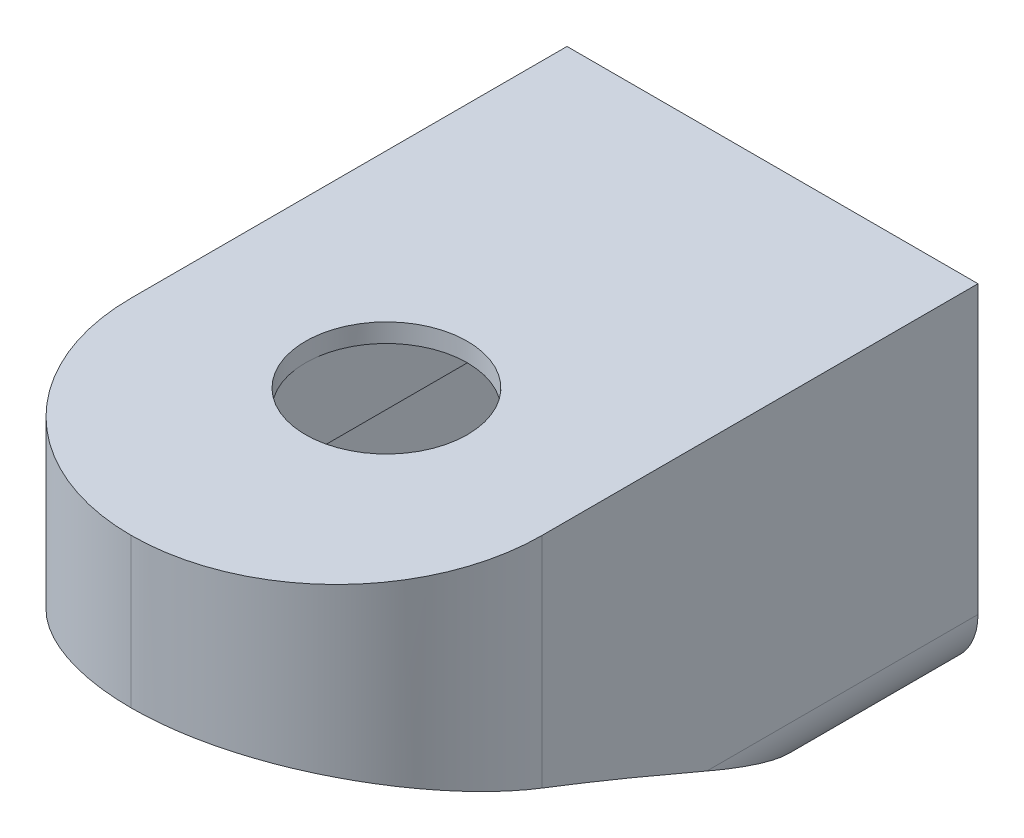
SolidWorks part; units mm, degrees
material "PETG"
ref_plane "Front Plane" through (0, 0, 0) normal (0, 0, 1) x (1, 0, 0)
ref_plane "Top Plane" through (0, 0, 0) normal (0, 1, 0) x (1, 0, 0)
ref_plane "Right Plane" through (0, 0, 0) normal (1, 0, 0) x (0, 0, -1)
sketch "Sketch1" plane through (0, 0, 0) normal (0, 0, 1) x (1, 0, 0)
  line L1 (-16.5, 14) -> (16.5, 14)
  line L2 (-16.5, 14) -> (-16.5, -14)
  line L3 (-16.5, -14) -> (16.5, -14)
  line L4 (16.5, 14) -> (16.5, -14)
  line L5 (-16.5, 14) -> (16.5, -14) construction
  line L6 (-16.5, -14) -> (16.5, 14) construction
  point P0 (0, 0)
  dimension "D1" = 33
  dimension "D2" = 28
extrude "Boss-Extrude1" add sketch "Sketch1" along normal blind 46
sketch "Sketch2" plane through (16.5, 0, 0) normal (1, 0, 0) x (0, 0, -1)
  line L0 (-46, -14) -> (0, -14) construction
  line L1 (-46, -14) -> (-46, 14) construction
  line L2 (-46, 14) -> (0, 14) construction
  spline S0 degree 2 poles (-5, -14) (-31.6429, -1.8661) (-46, 2) knots 0 0 0 1 1 1
  dimension "D1" = 5
  dimension "D2" = 12
extrude "Cut-Extrude1" cut sketch "Sketch2" against normal through all and the other way through all
sketch "Sketch3" plane through (16.5, 0, 0) normal (1, 0, 0) x (0, 0, -1)
  line L0 (-5, -14) -> (-2.5, -14)
  line L2 (-2.5, -14) -> (-2.5, 3.5)
  line L3 (-2.5, 3.5) -> (-40.5, 3.5)
  line L4 (-40.5, 3.5) -> (-40.5, 0.3618)
  parabola Q0 (-5, -14) -> (-46, 2) focus (-60.8957, 1.0115) apex (-62.1909, 1.8831) construction
  parabola Q1 (-5, -14) -> (-46, 2) focus (-60.8957, 1.0115) apex (-62.1909, 1.8831) construction
  parabola Q2 (-5, -14) -> (-46, 2) focus (-60.8957, 1.0115) apex (-62.1909, 1.8831) construction
  parabola Q3 (-5, -14) -> (-40.5, 0.3618) focus (-60.8957, 1.0115) apex (-62.1909, 1.8831)
  dimension "D1" = 38
  dimension "D2" = 17.5
  dimension "D3" = 2.5
extrude "Cut-Extrude2" cut sketch "Sketch3" against normal blind 27 from offset 3 offset against normal yes
fillet "Fillet1" radius 12.5 2 edges at (13.5, 1.9309, 40.5) (-13.5, 1.9309, 40.5)
fillet "Fillet2" radius 16.5 2 edges at (16.5, 8, 46) (-16.5, 8, 46)
fillet "Fillet3" radius 5 2 edges at (16.5, -14, 2.5) (-16.5, -14, 2.5)
sketch "Sketch4" plane through (0, 3.5, 0) normal (0, -1, 0) x (1, 0, 0)
  line L0 (0, 46) -> (0, 0) construction
  line L1 (-13.5, 2.5) -> (13.5, 2.5) construction
  line L2 (-6.5, 32) -> (6.5, 32)
  line L3 (-6.5, 32) -> (-6.5, 9)
  line L4 (-6.5, 9) -> (6.5, 9)
  line L5 (6.5, 32) -> (6.5, 9)
  line L6 (-6.5, 32) -> (6.5, 9) construction
  line L7 (-6.5, 9) -> (6.5, 32) construction
  point P4 (0, 20.5)
  dimension "D1" = 6.5
  dimension "D2" = 23
  dimension "D3" = 13
extrude "Cut-Extrude3" cut sketch "Sketch4" against normal blind 9
sketch "Sketch5" plane through (0, 12.5, 0) normal (0, -1, 0) x (1, 0, 0)
  line L0 (0, 32) -> (0, 9) construction
  line L1 (6.5, 32) -> (-6.5, 32) construction
  line L2 (-6.5, 9) -> (6.5, 9) construction
  circle A0 centre (0, 25.5) radius 6.5
  dimension "D1" = 13
extrude "Cut-Extrude4" cut sketch "Sketch5" against normal through all
sketch "Sketch6" plane through (0, 3.5, 0) normal (0, -1, 0) x (1, 0, 0)
  line L0 (-6.5, 20.5) -> (6.5, 20.5) construction
  line L1 (-6.5, 32) -> (-6.5, 9) construction
  line L2 (6.5, 9) -> (6.5, 32) construction
  line L3 (0, 34.3) -> (0, 6.7) construction
  circle A0 centre (0, 34.3) radius 1
  circle A1 centre (0, 6.7) radius 1
  point P10 (0, 20.5)
  dimension "D2" = 2
  dimension "D1" = 27.6
extrude "Cut-Extrude5" cut sketch "Sketch6" against normal blind 8
sketch "Sketch10" plane through (0, 0, 0) normal (0, 0, -1) x (-1, 0, 0)
  line L4 (-16.5, 14) -> (-16.5, -9)
  line L5 (-11.5, -14) -> (11.5, -14)
  line L6 (16.5, -9) -> (16.5, 14)
  line L7 (16.5, 14) -> (-16.5, 14)
  line L8 (-16.5, 14) -> (-16.5, -9)
  line L9 (-11.5, -14) -> (11.5, -14)
  line L10 (16.5, -9) -> (16.5, 14)
  line L11 (16.5, 14) -> (-16.5, 14)
  arc A2 (-16.5, -9) -> (-11.5, -14) centre (-11.5, -9) ccw
  arc A3 (11.5, -14) -> (16.5, -9) centre (11.5, -9) ccw
  arc A4 (-16.5, -9) -> (-11.5, -14) centre (-11.5, -9) ccw
  arc A5 (11.5, -14) -> (16.5, -9) centre (11.5, -9) ccw
  dimension "D1" = 0
extrude "Boss-Extrude2" add sketch "Sketch10" along normal blind 5.5
sketch "Sketch11" plane through (0, 0, -5.5) normal (0, 0, -1) x (-1, 0, 0)
  line L0 (0, 0) -> (-16.5, 0.2665) construction
  line L1 (-16.5, 14) -> (-16.5, -9) construction
  circle A0 centre (1, -0.0162) radius 13.5
  dimension "D2" = 27
  dimension "17.5" = 17.5
extrude "Cut-Extrude8" cut sketch "Sketch11" against normal blind 7.5
sketch "Sketch7" plane through (0, 0, 2) normal (0, 0, -1) x (-1, 0, 0)
  line L0 (0, 0) -> (-16.5, 0) construction
  line L2 (-16.5, 14) -> (-16.5, -9) construction
  circle A0 centre (5.25, 0) radius 1.3
  circle A1 centre (-4.75, 0) radius 2.6
  circle A2 centre (0.25, 0) radius 1.3
  point P10 (4.2262, 0)
  point P11 (0, 0)
  point P13 (0, 0)
  point P14 (0, 0)
  dimension "D1" = 2.6
  dimension "D2" = 5.2
  dimension "D3" = 11.75
  dimension "D4" = 5
  dimension "D5" = 5
extrude "Cut-Extrude6" cut sketch "Sketch7" against normal up to surface (0.5 mm away) up to face at (0, -8.0619, 2.5)
sketch "Sketch12" plane through (0, 3.5, 0) normal (0, -1, 0) x (1, 0, 0)
  line L0 (-6.5, 9) -> (6.5, 9) construction
  line L1 (6.5, 9) -> (6.5, 32) construction
  line L2 (6.5, 32) -> (-6.5, 32) construction
  line L3 (0, 32) -> (-6.5, 32) construction
  line L4 (13.5, 2.5) -> (13.5, 28)
  line L5 (1, 40.5) -> (-1, 40.5)
  line L6 (-13.5, 28) -> (-13.5, 2.5)
  line L7 (-13.5, 2.5) -> (13.5, 2.5)
  line L8 (13.5, 2.5) -> (13.5, 28)
  line L9 (1, 40.5) -> (-1, 40.5)
  line L10 (-13.5, 28) -> (-13.5, 2.5)
  line L11 (-13.5, 2.5) -> (13.5, 2.5)
  line L12 (-6.5, 32) -> (-6.5, 9) construction
  line L13 (-6.5, 9) -> (6.5, 9)
  line L14 (6.5, 9) -> (6.5, 32)
  line L15 (6.5, 32) -> (-6.5, 32)
  line L16 (0, 32) -> (-6.5, 32)
  line L17 (-6.5, 32) -> (-6.5, 9)
  line L18 (-6.5, 32) -> (-6.5, 9)
  circle A0 centre (0, 34.3) radius 1 construction
  circle A1 centre (0, 34.3) radius 1
  arc A2 (13.5, 28) -> (1, 40.5) centre (1, 28) ccw
  arc A3 (-1, 40.5) -> (-13.5, 28) centre (-1, 28) ccw
  arc A4 (13.5, 28) -> (1, 40.5) centre (1, 28) ccw
  arc A5 (-1, 40.5) -> (-13.5, 28) centre (-1, 28) ccw
  circle A6 centre (0, 6.7) radius 1 construction
  circle A7 centre (0, 6.7) radius 1
  circle M8 centre (0, 34.3) radius 1
  circle M9 centre (0, 6.7) radius 1
  line M10 (13.5, 2.5) -> (13.5, 28)
  arc M11 (13.5, 28) -> (1, 40.5) centre (1, 28) ccw
  line M12 (1, 40.5) -> (-1, 40.5)
  arc M13 (-1, 40.5) -> (-13.5, 28) centre (-1, 28) ccw
  line M14 (-13.5, 28) -> (-13.5, 2.5)
  line M15 (-13.5, 2.5) -> (13.5, 2.5)
  line M16 (6.5, 32) -> (6.5, 9)
  line M17 (6.5, 9) -> (-6.5, 9)
  line M18 (-6.5, 9) -> (-6.5, 32)
  line M19 (-6.5, 32) -> (6.5, 32)
  dimension "D1" = 0
extrude "Cut-Extrude9" cut sketch "Sketch12" against normal blind 2.5 contours L15 M15 M10 M11 M12 M13 M14 M9 M19 M16 M17 M18 M8
